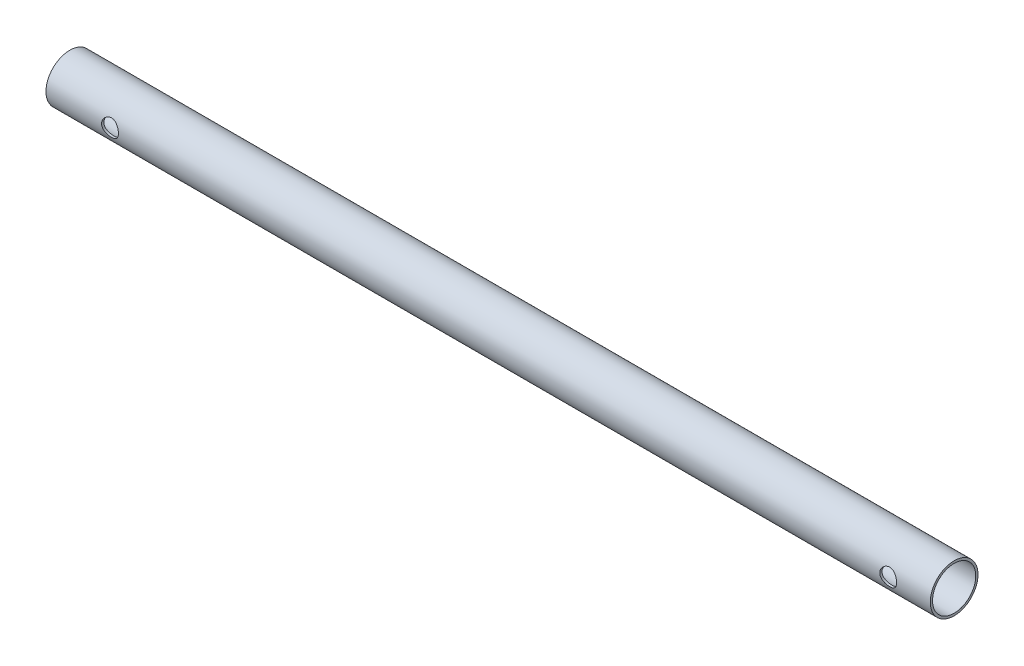
SolidWorks part; units mm, degrees
ref_plane "Front Plane" through (0, 0, 0) normal (0, 0, 1) x (1, 0, 0)
ref_plane "Top Plane" through (0, 0, 0) normal (0, 1, 0) x (1, 0, 0)
ref_plane "Right Plane" through (0, 0, 0) normal (1, 0, 0) x (0, 0, -1)
sketch "Sketch1" plane through (0, 0, 0) normal (1, 0, 0) x (0, 0, -1)
  circle A0 centre (0, 0) radius 8.5
  circle A1 centre (0, 0) radius 7.7
  dimension "D1" = 0.8
extrude "Boss-Extrude1" add sketch "Sketch1" along normal blind 315
sketch "Sketch2" plane through (0, 0, 0) normal (0, 0, 1) x (1, 0, 0)
  line L0 (0, 8.5) -> (0, -8.5) construction
  line L1 (315, -8.5) -> (315, 8.5) construction
  circle A0 centre (22.8, 0) radius 3
  circle A1 centre (300, 0) radius 3
  dimension "D1" = 22.8
  dimension "D2" = 15
extrude "Cut-Extrude1" cut sketch "Sketch2" against normal blind 320 and the other way blind 320
